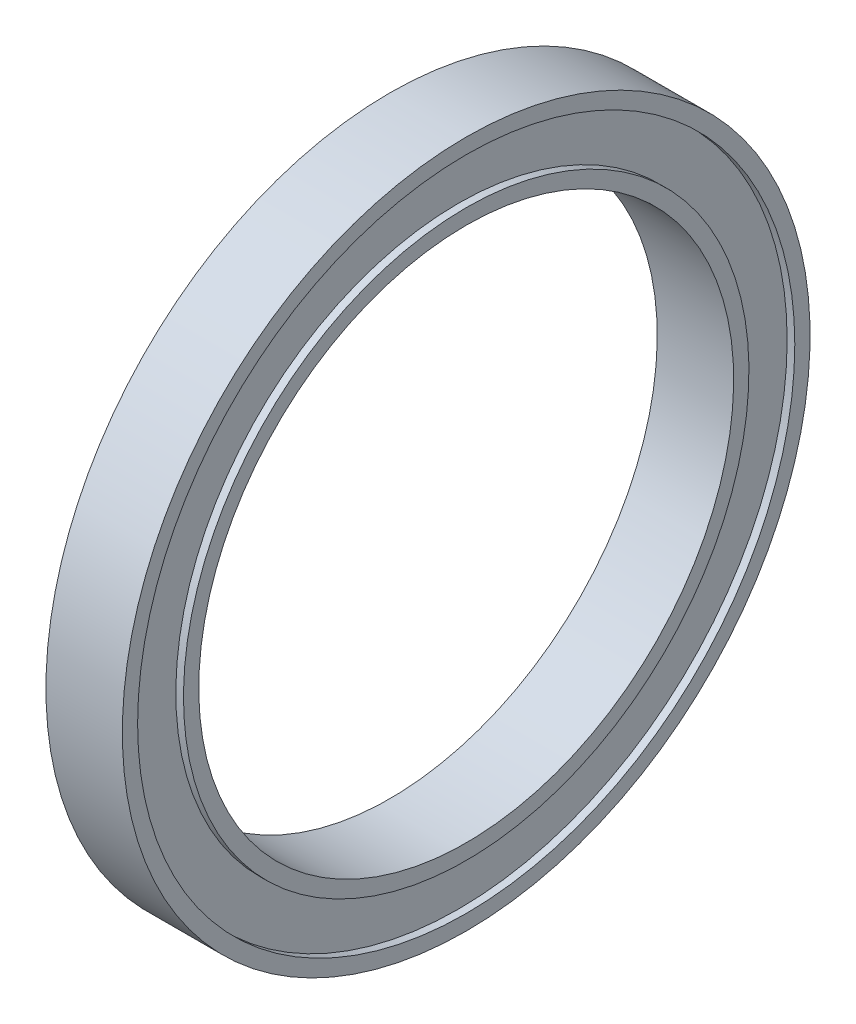
SolidWorks part; units mm, degrees
material "AISI 316 Stainless Steel Sheet (SS)"
ref_plane "Front Plane" through (0, 0, 0) normal (0, 0, 1) x (1, 0, 0)
ref_plane "Top Plane" through (0, 0, 0) normal (0, 1, 0) x (1, 0, 0)
ref_plane "Right Plane" through (0, 0, 0) normal (1, 0, 0) x (0, 0, -1)
sketch "Sketch1" plane through (0, 0, 0) normal (0, 0, 1) x (1, 0, 0)
  line L0 (6.4812, 0) -> (0, 0) construction
  line L1 (-5, 35) -> (5, 35)
  line L2 (5, 35) -> (5, 37)
  line L3 (5, 37) -> (4, 37)
  line L4 (4, 37) -> (4, 43)
  line L5 (4, 43) -> (5, 43)
  line L6 (5, 43) -> (5, 45)
  line L7 (5, 45) -> (-5, 45)
  line L8 (0, 45) -> (0, 35) construction
  line L9 (0, 35) -> (0, 0) construction
  line L10 (-5, 43) -> (-5, 45)
  line L11 (-4, 43) -> (-5, 43)
  line L12 (-4, 37) -> (-4, 43)
  line L13 (-5, 37) -> (-4, 37)
  line L14 (-5, 35) -> (-5, 37)
  line L15 (4, 43) -> (4, 44) construction
  line L16 (5, 43) -> (5, 41) construction
  line L17 (5, 41) -> (5, 39) construction
  line L18 (5, 39) -> (5, 37) construction
  point P21 (5, 44)
  dimension "D1" = 70
  dimension "D2" = 90
  dimension "D4" = 10
revolve "Revolve1" add sketch "Sketch1" angle 360 about L0
equation "\"d_i\"= 70"
equation "\"D1@Sketch1\"=\"d_i\""
equation "\"d_o\"= 90"
equation "\"w\"= 10"
equation "\"D4@Sketch1\"=\"w\""
equation "\"D2@Sketch1\"=\"d_o\""
